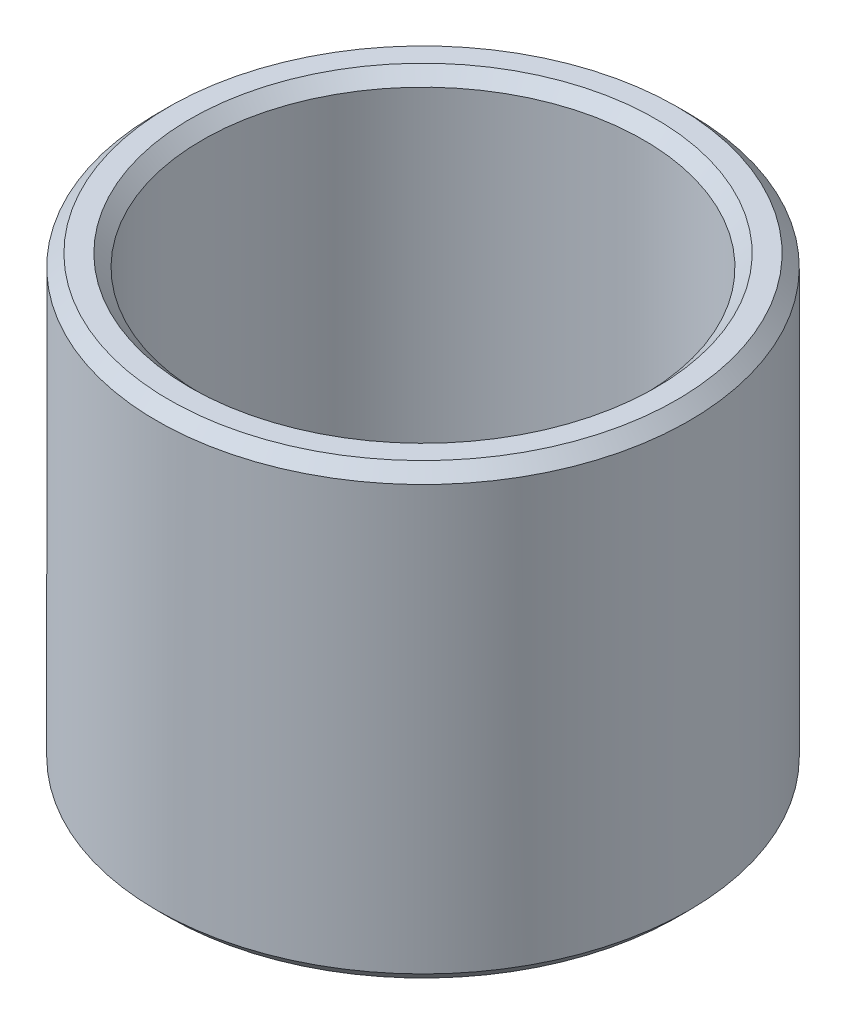
SolidWorks part; units mm, degrees
ref_plane "Front Plane" through (0, 0, 0) normal (0, 0, 1) x (1, 0, 0)
ref_plane "Top Plane" through (0, 0, 0) normal (0, 1, 0) x (1, 0, 0)
ref_plane "Right Plane" through (0, 0, 0) normal (1, 0, 0) x (0, 0, -1)
sketch "Sketch1" plane through (0, 0, 0) normal (0, 1, 0) x (1, 0, 0)
  circle A0 centre (0, 0) radius 47.5
  dimension "SLEEVE_OD" = 95
extrude "Boss-Extrude1" add sketch "Sketch1" along normal blind 80.0022
sketch "Sketch2" plane through (0, 0, 0) normal (0, 1, 0) x (1, 0, 0)
  circle A0 centre (0, 0) radius 39.3825
  dimension "BORE_D" = 78.765
extrude "Cut-Extrude1" cut sketch "Sketch2" along normal through all
chamfer "Chamfer1" distance 2.1693 angle 45 4 edges at (0, 80.0022, 39.3825) (0, 0, 39.3825) (0, 0, 47.5) (0, 80.0022, 47.5)
